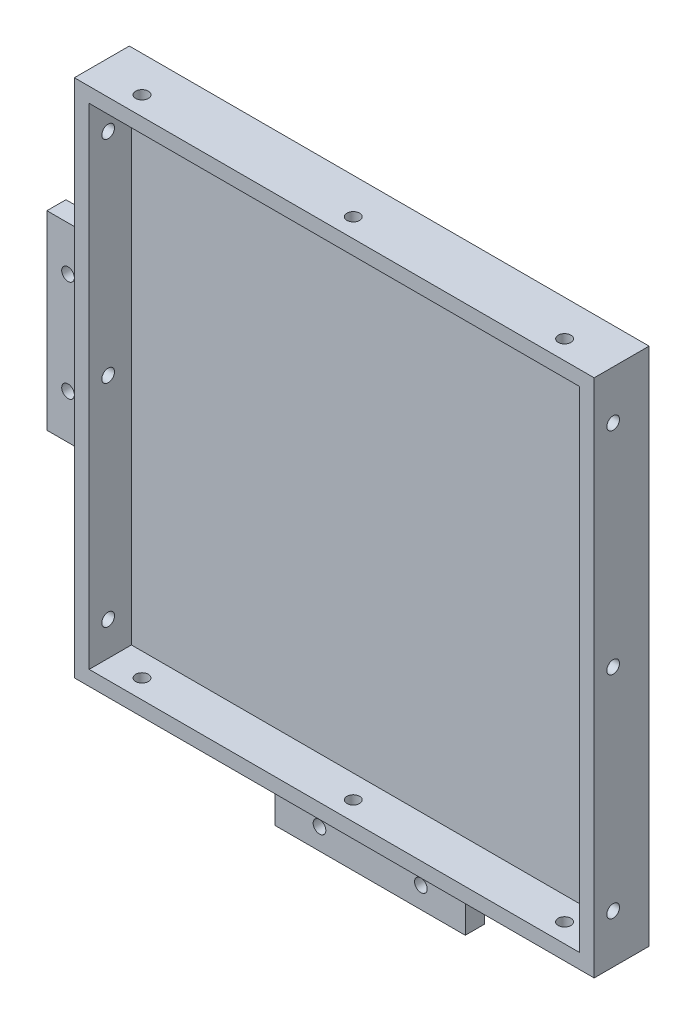
SolidWorks part; units mm, degrees
ref_plane "前视基准面" through (0, 0, 0) normal (0, 0, 1) x (1, 0, 0)
ref_plane "上视基准面" through (0, 0, 0) normal (0, 1, 0) x (1, 0, 0)
ref_plane "右视基准面" through (0, 0, 0) normal (1, 0, 0) x (0, 0, -1)
sketch "草图3" plane through (0, 0, 0) normal (0, 0, 1) x (1, 0, 0)
  line L1 (61.5, -61.5) -> (-61.5, -61.5)
  line L2 (61.5, -61.5) -> (61.5, 61.5)
  line L3 (61.5, 61.5) -> (-61.5, 61.5)
  line L4 (-61.5, -61.5) -> (-61.5, 61.5)
  line L5 (61.5, -61.5) -> (-61.5, 61.5) construction
  line L6 (61.5, 61.5) -> (-61.5, -61.5) construction
  point P0 (0, 0)
  dimension "D1" = 123
  dimension "D2" = 123
extrude "凸台-拉伸2" add sketch "草图3" along normal blind 3
sketch "草图4" plane through (0, 0, 3) normal (0, 0, 1) x (1, 0, 0)
  line L0 (61.5, -61.5) -> (61.5, 61.5) construction
  line L1 (58, -58) -> (-58, -58)
  line L2 (58, -58) -> (58, 58)
  line L3 (58, 58) -> (-58, 58)
  line L4 (-58, -58) -> (-58, 58)
  line L5 (58, -58) -> (-58, 58) construction
  line L6 (58, 58) -> (-58, -58) construction
  line L7 (-61.5, -61.5) -> (61.5, -61.5) construction
  line L12 (-61.5, 61.5) -> (-61.5, -61.5)
  line L13 (-61.5, -61.5) -> (61.5, -61.5)
  line L14 (61.5, -61.5) -> (61.5, 61.5)
  line L15 (61.5, 61.5) -> (-61.5, 61.5)
  line L16 (-61.5, 61.5) -> (-61.5, -61.5)
  line L17 (-61.5, -61.5) -> (61.5, -61.5)
  line L18 (61.5, -61.5) -> (61.5, 61.5)
  line L19 (61.5, 61.5) -> (-61.5, 61.5)
  point P0 (0, 0)
  point P6 (58, 0)
  dimension "D1" = 3.5
  dimension "D2" = 3.5
  dimension "D3" = 0
extrude "凸台-拉伸3" add sketch "草图4" along normal blind 10 contours L16 L17 L18 L19 | L2 L1 L4 L3
sketch "草图7" plane through (0, -61.5, 0) normal (0, -1, 0) x (1, 0, 0)
  line L0 (0, 13) -> (0, 8.5) construction
  line L1 (-61.5, 13) -> (61.5, 13) construction
  circle A0 centre (0, 8.5) radius 1.5
  circle A1 centre (50, 8.5) radius 1.5
  circle A2 centre (-50, 8.5) radius 1.5
  dimension "D2" = 3
  dimension "D1" = 4.5
  dimension "D3" = 2
  dimension "D4" = 2
extrude "切除-拉伸1" cut sketch "草图7" against normal through all
sketch "草图9" plane through (-61.5, 0, 0) normal (-1, 0, 0) x (0, 0, 1)
  line L0 (13, 0) -> (8.5, 0) construction
  line L1 (13, 61.5) -> (13, -61.5) construction
  circle A0 centre (8.5, 0) radius 1.5
  circle A1 centre (8.5, -50) radius 1.5
  circle A2 centre (8.5, 50) radius 1.5
  dimension "D2" = 3
  dimension "D1" = 4.5
  dimension "D3" = 2
  dimension "D4" = 2
extrude "切除-拉伸2" cut sketch "草图9" against normal through all
sketch "草图10" plane through (0, 0, 0) normal (0, 0, -1) x (-1, 0, 0)
  line L0 (61.5, -61.5) -> (-61.5, -61.5) construction
  line L1 (22.5, -76.5) -> (-22.5, -76.5)
  line L2 (22.5, -76.5) -> (22.5, -61.5)
  line L4 (-22.5, -76.5) -> (-22.5, -61.5)
  line L5 (22.5, -76.5) -> (-20.0743, -48.1171) construction
  line L6 (20.0743, -48.1171) -> (-22.5, -76.5) construction
  line L7 (-22.5, -61.5) -> (22.5, -61.5)
  point P0 (0, -61.5)
  dimension "D1" = 45
  dimension "D2" = 15
extrude "凸台-拉伸4" add sketch "草图10" against normal blind 4.5
sketch "草图11" plane through (0, 0, 4.5) normal (0, 0, 1) x (1, 0, 0)
  line L0 (0, -76.5) -> (0, -71.5)
  line L1 (22.5, -76.5) -> (-22.5, -76.5) construction
  line L2 (0, -71.5) -> (-12, -71.5) construction
  circle A0 centre (-12, -71.5) radius 1.5
  circle A1 centre (12, -71.5) radius 1.5
  dimension "D3" = 3
  dimension "D1" = 5
  dimension "D2" = 12
extrude "切除-拉伸3" cut sketch "草图11" against normal through all contours A0 | A1 region at (-12, -71.5, 4.5) region at (12, -71.5, 4.5)
sketch "草图12" plane through (0, 0, 13) normal (0, 0, 1) x (1, 0, 0)
  line L0 (-61.5, -61.5) -> (-58, -58) construction
ref_axis "基准轴1" through (0, 0, 13.65) along (0, 0, -1)
pattern_circular "阵列(圆周)1" count 2 every 90 about axis through (0, 0, 13.65) along (0, 0, -1) of "凸台-拉伸4", "切除-拉伸3"
fillet "圆角1" radius 8 6 edges at (22.5, -61.5, 2.25) (-22.5, -61.5, 2.25) (0, -61.5, 4.5) (-61.5, -22.5, 2.25) (-61.5, 22.5, 2.25) (-61.5, 0, 4.5)
sketch "草图13" plane through (-61.5, 0, 0) normal (-1, 0, 0) x (0, 0, 1)
  circle A0 centre (8.5, 0) radius 3
  dimension "D1" = 6
extrude "切除-拉伸4" cut sketch "草图13" along normal through all
sketch "草图14" plane through (0, -61.5, 0) normal (0, -1, 0) x (1, 0, 0)
  circle A0 centre (0, 8.5) radius 2.0492
extrude "切除-拉伸6" cut sketch "草图14" along normal through all contours A0
